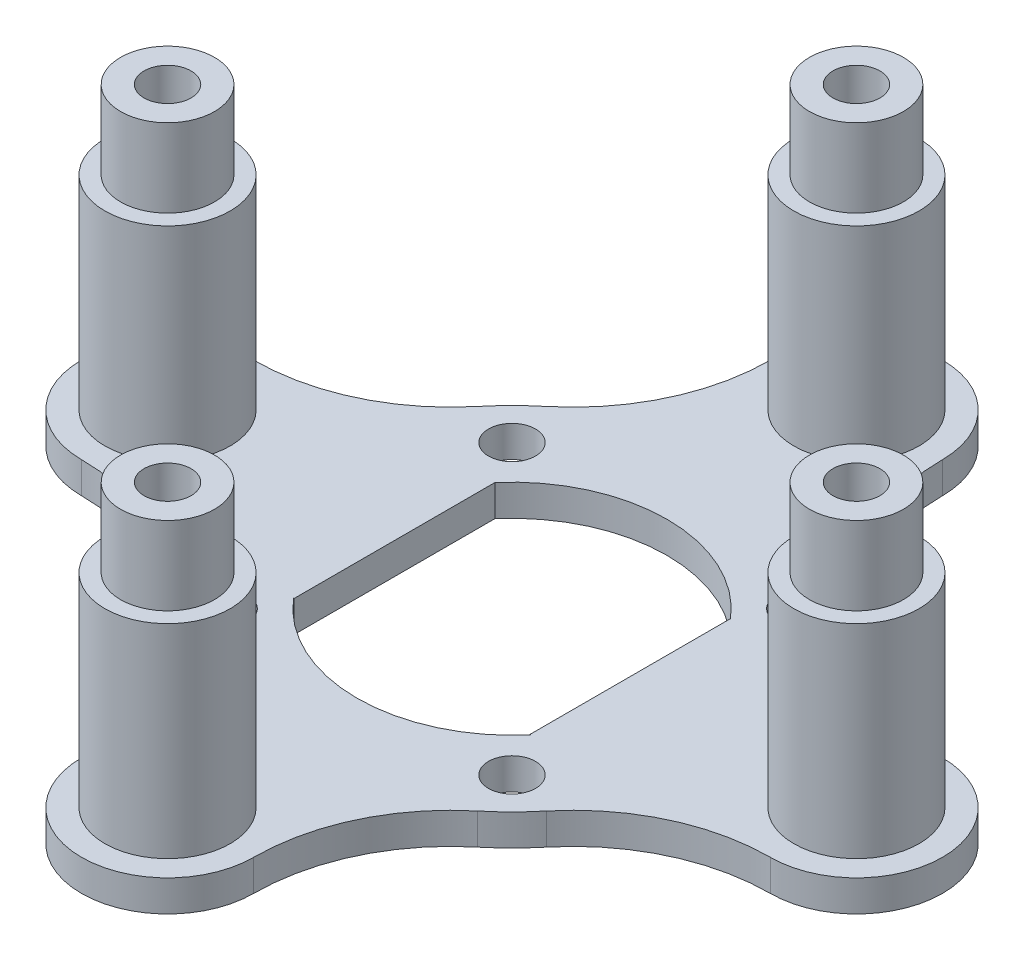
SolidWorks part; units mm, degrees
ref_plane "Front Plane" through (0, 0, 0) normal (0, 0, 1) x (1, 0, 0)
ref_plane "Top Plane" through (0, 0, 0) normal (0, 1, 0) x (1, 0, 0)
ref_plane "Right Plane" through (0, 0, 0) normal (1, 0, 0) x (0, 0, -1)
sketch "Sketch1" plane through (0, 0, 0) normal (0, 1, 0) x (1, 0, 0)
  line L0 (-7.5263, -6.3887) -> (-7.5627, -6.3887)
  line L1 (7.5627, -6.3887) -> (7.5263, -6.3887)
  line L2 (7.5263, -6.3887) -> (7.5263, 6.4316)
  line L3 (-7.5263, 6.4316) -> (-7.5263, -6.3887)
  line L4 (-9.1924, 9.1924) -> (-9.1924, -9.1924) construction
  line L5 (-9.1924, 9.1924) -> (9.1924, 9.1924) construction
  line L6 (-9.1924, -9.1924) -> (9.1924, -9.1924) construction
  line L7 (9.1924, 9.1924) -> (9.1924, -9.1924) construction
  line L8 (-9.1924, 9.1924) -> (9.1924, -9.1924) construction
  line L9 (-9.1924, -9.1924) -> (9.1924, 9.1924) construction
  arc A0 (-7.5627, -6.3887) -> (7.5627, -6.3887) centre (0, 0) ccw
  arc A1 (7.5263, 6.4316) -> (-7.5263, 6.4316) centre (0, 0) ccw
  circle A2 centre (0, 0) radius 15.9
  circle A3 centre (-9.1924, 9.1924) radius 1.5
  circle A4 centre (9.1924, 9.1924) radius 1.5
  circle A5 centre (9.1924, -9.1924) radius 1.5
  circle A6 centre (-9.1924, -9.1924) radius 1.5
  point P24 (0, 0)
  dimension "D1" = 31.8
  dimension "D3" = 9.9
  dimension "D6" = 3
  dimension "D2" = 12.8202
  dimension "D4" = 15.089
  dimension "D5" = 13
  dimension "D7" = 4
sketch "Sketch2" plane through (0, 0, 0) normal (0, 1, 0) x (1, 0, 0)
  line L0 (0, 0) -> (155.6578, 0) construction
  line L1 (-7.5263, 6.4316) -> (-7.5263, -6.3887) construction
  line L2 (-7.5263, -6.3887) -> (-7.5627, -6.3887) construction
  line L3 (7.5627, -6.3887) -> (7.5263, -6.3887) construction
  line L4 (7.5263, -6.3887) -> (7.5263, 6.4316) construction
  line L5 (-7.5263, 6.4316) -> (-7.5263, -6.3887)
  line L6 (-7.5263, -6.3887) -> (-7.5627, -6.3887)
  line L7 (7.5627, -6.3887) -> (7.5263, -6.3887)
  line L8 (7.5263, -6.3887) -> (7.5263, 6.4316)
  circle A0 centre (22, 0) radius 1.5
  circle A1 centre (22, 0) radius 4
  circle A2 centre (22, 0) radius 3
  circle A12 centre (22, 0) radius 5.5
  arc A13 (12.2869, 10.0916) -> (22, 5.5) centre (22, 18.0692) ccw
  arc A14 (12.2869, -10.0916) -> (22, -5.5) centre (22, -18.0692) cw
  circle A15 centre (0, 0) radius 15.9 construction
  circle A16 centre (0, 0) radius 15.9
  arc A17 (10.0916, -12.2869) -> (5.5, -22) centre (18.0692, -22) ccw
  circle A18 centre (0, -22) radius 5.5
  circle A19 centre (0, -22) radius 4
  circle A20 centre (0, -22) radius 3
  circle A21 centre (0, -22) radius 1.5
  arc A22 (-10.0916, -12.2869) -> (-5.5, -22) centre (-18.0692, -22) cw
  arc A23 (-12.2869, -10.0916) -> (-22, -5.5) centre (-22, -18.0692) ccw
  circle A24 centre (-22, 0) radius 5.5
  circle A25 centre (-22, 0) radius 4
  circle A26 centre (-22, 0) radius 3
  circle A27 centre (-22, 0) radius 1.5
  arc A28 (-12.2869, 10.0916) -> (-22, 5.5) centre (-22, 18.0692) cw
  arc A29 (-10.0916, 12.2869) -> (-5.5, 22) centre (-18.0692, 22) ccw
  circle A30 centre (0, 22) radius 5.5
  circle A31 centre (0, 22) radius 4
  circle A32 centre (0, 22) radius 3
  circle A33 centre (0, 22) radius 1.5
  arc A34 (10.0916, 12.2869) -> (5.5, 22) centre (18.0692, 22) cw
  arc A35 (-7.5627, -6.3887) -> (7.5627, -6.3887) centre (0, 0) ccw construction
  arc A36 (7.5263, 6.4316) -> (-7.5263, 6.4316) centre (0, 0) ccw construction
  circle A37 centre (9.1924, 9.1924) radius 1.5 construction
  circle A38 centre (9.1924, -9.1924) radius 1.5 construction
  circle A39 centre (-9.1924, -9.1924) radius 1.5 construction
  circle A40 centre (-9.1924, 9.1924) radius 1.5 construction
  arc A41 (-7.5627, -6.3887) -> (7.5627, -6.3887) centre (0, 0) ccw
  arc A42 (7.5263, 6.4316) -> (-7.5263, 6.4316) centre (0, 0) ccw
  circle A43 centre (9.1924, 9.1924) radius 1.5
  circle A44 centre (9.1924, -9.1924) radius 1.5
  circle A45 centre (-9.1924, -9.1924) radius 1.5
  circle A46 centre (-9.1924, 9.1924) radius 1.5
  point P19 (0, 0)
  point P54 (0, 0)
  dimension "D1" = 3
  dimension "D2" = 6
  dimension "D3" = 8
  dimension "D4" = 11
  dimension "D5" = 22
  dimension "D6" = 4
extrude "Boss-Extrude1" add sketch "Sketch2" along normal blind 2 contours A42 L8 A16 L7 A41 L6 L5 A46 A45 A44 A43 | A16 A22 A18 A17 | L0 A16 A14 A12 | A16 L0 A12 A13 | A12 L0 A1 | A1 L0 A2 | A2 L0 A0 | L0 A12 A1 | L0 A1 A2 | L0 A2 A0 | A18 A19 | A21 | A16 A34 A30 A29 | A30 A31 | A31 A32 | A32 A33 | A24 A25 | A25 A26 | A26 A27 | A16 A28 A24 A23 | A19 region at (22, 0, -1.5671) region at (24.25, 0, 0.0671) region at (22, 0, -3.0894) region at (25.5, 0, 0.0894) region at (22, 0, -4.123) region at (26.75, 0, 0.123) region at (16.6203, 0, -4.8104) region at (16.6203, 0, 4.8104) region at (14.5461, 0, -5.2079) region at (0, 0, -16.124) region at (6.5032, 0, 16.5324) region at (0, 0, -16.6556) region at (0, 0, 27.3444) region at (-16.124, 0, 0) region at (-18.2209, 0, -3.7791) region at (0, 0, 22) region at (-25.8869, 0, 0) region at (-24.9151, 0, 0) region at (-3.8869, 0, -22) region at (-2.9151, 0, -22)
extrude "Boss-Extrude2" add sketch "Sketch2<4>" along normal blind 20 contours A19 A20 | A20 A21 | L0 A1 A2 | L0 A2 A0 | A2 L0 A0 | A1 L0 A2 | A31 A32 | A32 A33 | A25 A26 | A27 | A26 region at (22, 0, -1.5671) region at (24.25, 0, 0.0671) region at (22, 0, -3.0894) region at (25.5, 0, 0.0894) region at (-3.8869, 0, 22) region at (-2.9151, 0, 22) region at (-25.8869, 0, 0) region at (-22, 0, 0) region at (-3.8869, 0, -22) region at (-2.9151, 0, -22)
sketch "Sketch2<4>" plane through (0, 0, 0) normal (0, 1, 0) x (1, 0, 0) same geometry as "Sketch2"
extrude "Cut-Extrude1" cut sketch "Sketch2<5>" against normal blind 5 from surface contours A25 A26 | A31 A32 | A1 L0 A2 | L0 A1 A2 | A19 A20 region at (22, 0, -3.0894) region at (25.5, 0, 0.0894) region at (-3.8869, 0, 22) region at (-25.8869, 0, 0) region at (-3.8869, 0, -22) starting at face at (0, 20, 26)
sketch "Sketch2<5>" plane through (0, 0, 0) normal (0, 1, 0) x (1, 0, 0) same geometry as "Sketch2"
sketch "Sketch3" plane through (0, 0, 0) normal (0, 1, 0) x (1, 0, 0)
  circle A0 centre (0, -22) radius 1.5 construction
  circle A1 centre (0, -22) radius 3 construction
  circle A2 centre (0, -22) radius 4 construction
  circle A3 centre (22, 0) radius 1.5 construction
  circle A4 centre (22, 0) radius 3 construction
  circle A5 centre (22, 0) radius 4 construction
  circle A6 centre (0, 22) radius 1.5 construction
  circle A7 centre (0, 22) radius 3 construction
  circle A8 centre (0, 22) radius 4 construction
  circle A9 centre (-22, 0) radius 1.5 construction
  circle A10 centre (-22, 0) radius 3 construction
  circle A11 centre (-22, 0) radius 4 construction
  circle A12 centre (0, -22) radius 1.5
  circle A13 centre (0, -22) radius 3
  circle A14 centre (0, -22) radius 4
  circle A15 centre (22, 0) radius 1.5
  arc A16 (22, -5.5) -> (22, 5.5) centre (22, 0) ccw
  arc A17 (12.2869, 10.0916) -> (22, 5.5) centre (22, 18.0692) ccw
  arc A18 (12.2869, 10.0916) -> (10.0916, 12.2869) centre (0, 0) ccw
  arc A19 (5.5, 22) -> (10.0916, 12.2869) centre (18.0692, 22) ccw
  arc A20 (5.5, 22) -> (-5.5, 22) centre (0, 22) ccw
  arc A21 (-10.0916, 12.2869) -> (-5.5, 22) centre (-18.0692, 22) ccw
  arc A22 (-10.0916, 12.2869) -> (-12.2869, 10.0916) centre (0, 0) ccw
  arc A23 (-22, 5.5) -> (-12.2869, 10.0916) centre (-22, 18.0692) ccw
  arc A24 (-22, 5.5) -> (-22, -5.5) centre (-22, 0) ccw
  arc A25 (-12.2869, -10.0916) -> (-22, -5.5) centre (-22, -18.0692) ccw
  arc A26 (-12.2869, -10.0916) -> (-10.0916, -12.2869) centre (0, 0) ccw
  arc A27 (-5.5, -22) -> (-10.0916, -12.2869) centre (-18.0692, -22) ccw
  arc A28 (-5.5, -22) -> (5.5, -22) centre (0, -22) ccw
  arc A29 (10.0916, -12.2869) -> (5.5, -22) centre (18.0692, -22) ccw
  arc A30 (10.0916, -12.2869) -> (12.2869, -10.0916) centre (0, 0) ccw
  arc A31 (22, -5.5) -> (12.2869, -10.0916) centre (22, -18.0692) ccw
  arc A32 (22, -5.5) -> (22, 5.5) centre (22, 0) ccw
  arc A33 (12.2869, 10.0916) -> (22, 5.5) centre (22, 18.0692) ccw
  arc A34 (12.2869, 10.0916) -> (10.0916, 12.2869) centre (0, 0) ccw
  arc A35 (5.5, 22) -> (10.0916, 12.2869) centre (18.0692, 22) ccw
  arc A36 (5.5, 22) -> (-5.5, 22) centre (0, 22) ccw
  arc A37 (-10.0916, 12.2869) -> (-5.5, 22) centre (-18.0692, 22) ccw
  arc A38 (-10.0916, 12.2869) -> (-12.2869, 10.0916) centre (0, 0) ccw
  arc A39 (-22, 5.5) -> (-12.2869, 10.0916) centre (-22, 18.0692) ccw
  arc A40 (-22, 5.5) -> (-22, -5.5) centre (-22, 0) ccw
  arc A41 (-12.2869, -10.0916) -> (-22, -5.5) centre (-22, -18.0692) ccw
  arc A42 (-12.2869, -10.0916) -> (-10.0916, -12.2869) centre (0, 0) ccw
  arc A43 (-5.5, -22) -> (-10.0916, -12.2869) centre (-18.0692, -22) ccw
  arc A44 (-5.5, -22) -> (5.5, -22) centre (0, -22) ccw
  arc A45 (10.0916, -12.2869) -> (5.5, -22) centre (18.0692, -22) ccw
  arc A46 (10.0916, -12.2869) -> (12.2869, -10.0916) centre (0, 0) ccw
  arc A47 (22, -5.5) -> (12.2869, -10.0916) centre (22, -18.0692) ccw
  circle A48 centre (22, 0) radius 3
  circle A49 centre (22, 0) radius 4
  circle A50 centre (0, 22) radius 1.5
  circle A51 centre (0, 22) radius 3
  circle A52 centre (0, 22) radius 4
  circle A53 centre (-22, 0) radius 1.5
  circle A54 centre (-22, 0) radius 3
  circle A55 centre (-22, 0) radius 4
  dimension "D1" = 0
